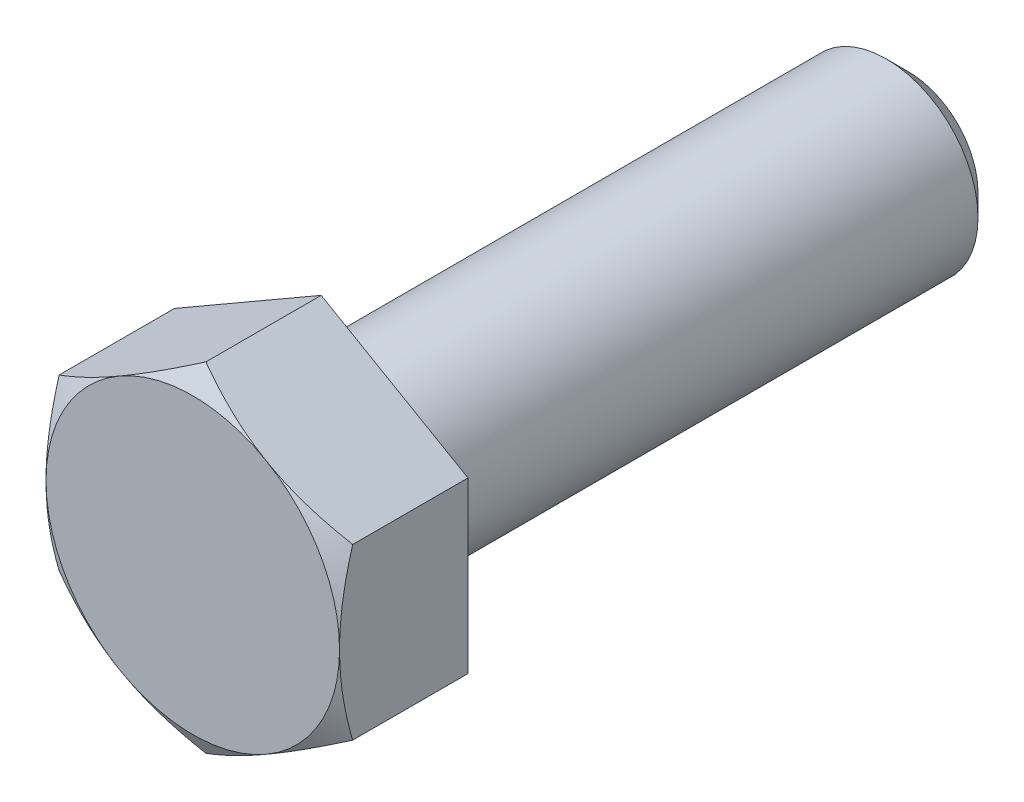
SolidWorks part; units mm, degrees
ref_plane "Front Plane" through (0, 0, 0) normal (0, 0, 1) x (1, 0, 0)
ref_plane "Top Plane" through (0, 0, 0) normal (0, 1, 0) x (1, 0, 0)
ref_plane "Right Plane" through (0, 0, 0) normal (1, 0, 0) x (0, 0, -1)
sketch "Sketch1" plane through (0, 0, 0) normal (1, 0, 0) x (0, 0, -1)
  line L0 (-9.75, 0) -> (9.75, 0) construction
  line L1 (-9.75, 0) -> (-9.75, 4)
  line L2 (-9.75, 4) -> (-6.25, 4)
  line L3 (-6.25, 4) -> (-6.25, 2.5)
  line L4 (-6.25, 2.5) -> (9.15, 2.5)
  line L5 (9.15, 2.5) -> (9.75, 1.9)
  line L6 (9.75, 1.9) -> (9.75, 0)
  line L7 (9.7, 2.5866) -> (10.1, 1.8938) construction
  line L8 (10.1, 1.8938) -> (10.5, 2.5866) construction
  line L9 (10.5, 2.5866) -> (9.7, 2.5866) construction
  line L10 (10.1, 1.8938) -> (10.1, 1.9804) construction
  line L11 (9.75, 2.5) -> (10.45, 2.5) construction
  line L12 (10.1, 2.5) -> (10.1, 2.5866) construction
  line L13 (9.15, 2.5) -> (9.75, 2.5) construction
  line L14 (10.475, 2.5433) -> (9.725, 2.5433) construction
  line L15 (9.75, 2.5) -> (9.75, 1.9) construction
  line L16 (10.05, 1.9804) -> (10.15, 1.9804) construction
  point P15 (10.1, 2.5433)
  point P17 (7.75, 2.5)
  point P19 (7.75, -2.5)
  dimension "D1" = 135
  dimension "Pitch" = 0.8
  dimension "D2" = 0.1
  dimension "Thread Diameter" = 5
  dimension "Length" = 16
  dimension "Head Height" = 3.5
  dimension "Head Width" = 8
  dimension "D3" = 0.6
  dimension "D4" = 2
sketch "Sketch2" plane through (0, 0, 0) normal (1, 0, 0) x (0, 0, -1)
  line L0 (-9.75, 4) -> (-9.75, 0)
  line L1 (-9.75, 0) -> (9.75, 0)
  line L2 (9.75, 0) -> (9.75, 1.9)
  line L3 (9.75, 1.9) -> (9.15, 2.5)
  line L4 (9.15, 2.5) -> (-6.25, 2.5)
  line L5 (-6.25, 2.5) -> (-6.25, 4)
  line L6 (-6.25, 4) -> (-9.75, 4)
revolve "Revolve1" add sketch "Sketch2" angle 360 about L1
sketch "Sketch3" plane through (0, 0, 9.75) normal (0, 0, 1) x (1, 0, 0)
  line L1 (0, 4.6188) -> (-4, 2.3094)
  line L2 (-4, 2.3094) -> (-4, -2.3094)
  line L3 (-4, -2.3094) -> (0, -4.6188)
  line L4 (0, -4.6188) -> (4, -2.3094)
  line L5 (4, -2.3094) -> (4, 2.3094)
  line L6 (4, 2.3094) -> (0, 4.6188)
  circle A0 centre (0, 0) radius 4 construction
extrude "Boss-Extrude1" add sketch "Sketch3" against normal up to surface (3.5 mm away) up to face at (4, 0, 6.25)
sketch "Sketch4" plane through (0, 0, 9.75) normal (0, 0, 1) x (1, 0, 0)
  circle A0 centre (0, 0) radius 4 construction
  circle A1 centre (0, 0) radius 4
extrude "Cut-Extrude1" cut sketch "Sketch4" against normal through all draft 60 flip side to cut
ref_axis "Center Axis 1" through (0, 0, 9.75) along (0, 0, -1)
sketch "Sketch6" [suppressed] plane through (0, 0, -9.75) normal (0, 0, -1) x (-1, 0, 0)
  circle A0 centre (0, 0) radius 2.5 construction
  circle A1 centre (0, 0) radius 2.5
split "Split1" [suppressed] bodies to split 106
curve "Helix/Spiral1" [suppressed] pitch 0.8 height 16.8 turns 21
sketch "Sketch7" [suppressed] plane through (0, 0, 0) normal (1, 0, 0) x (0, 0, -1)
  line L0 (9.725, 2.5433) -> (10.05, 1.9804)
  line L1 (10.05, 1.9804) -> (10.15, 1.9804)
  line L2 (10.15, 1.9804) -> (10.475, 2.5433)
  line L3 (10.475, 2.5433) -> (9.725, 2.5433)
sweep "Cut-Sweep1" [suppressed] cut profiles "Sketch7" path "Helix/Spiral1"
sketch "Sketch8" [suppressed] plane through (0, 0, 6.25) normal (0, 0, -1) x (-1, 0, 0)
  circle A0 centre (0, 0) radius 2.5 construction
  circle A1 centre (0, 0) radius 2.5
extrude "Boss-Extrude2" [suppressed] add sketch "Sketch8" along normal up to body draft 20 separate body
equation "\"D2@Sketch1\"=\"Pitch@Sketch1\"/8"
equation "\"D3@Sketch1\"=\"Pitch@Sketch1\"*.75"
equation "\"D4@Helix/Spiral1\"=\"Pitch@Sketch1\""
equation "\"D3@Helix/Spiral1\"=\"Length@Sketch1\"+\"Pitch@Sketch1\""
equation "\"D4@Sketch1\"=2.5*\"Pitch@Sketch1\""
